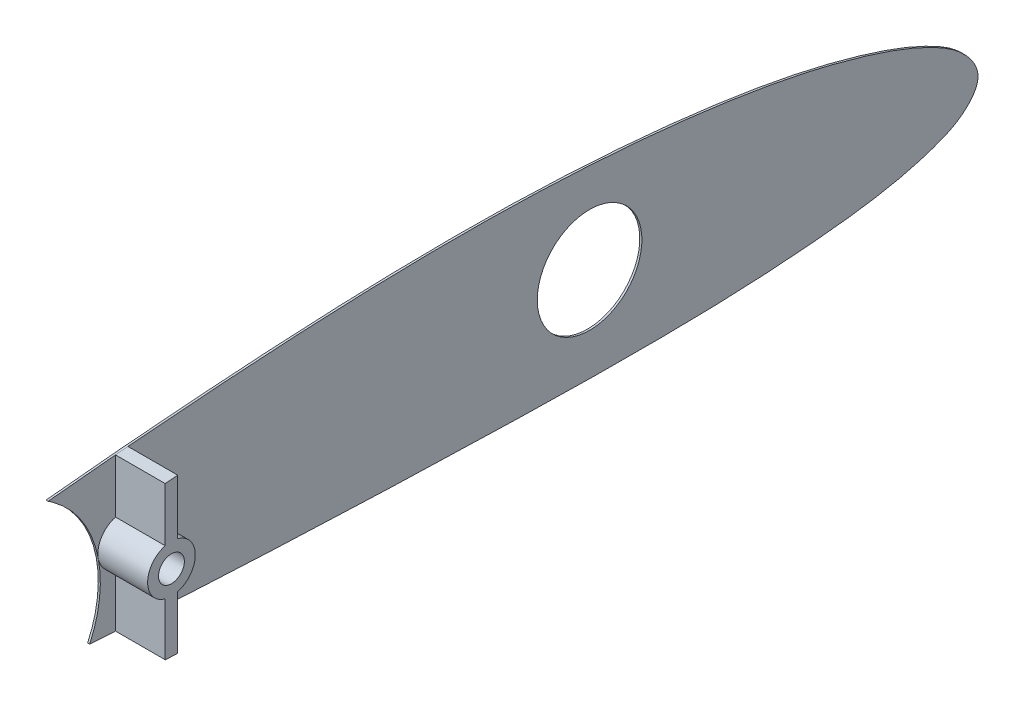
SolidWorks part; units mm, degrees
material "ABS"
ref_plane "Front Plane" through (0, 0, 0) normal (0, 0, 1) x (1, 0, 0)
ref_plane "Top Plane" through (0, 0, 0) normal (0, 1, 0) x (1, 0, 0)
ref_plane "Right Plane" through (0, 0, 0) normal (1, 0, 0) x (0, 0, -1)
body saved out of another part "Stock-NACA2412_3Dmodel_test-1" rebuild error yes
sketch "Sketch15" plane through (1117, 0, 0) normal (-1, 0, 0) x (0, 0, 1)
  line L0 (74.9825, 5.5405) -> (165.3194, 5.5405) construction
  line L1 (165.3194, 5.5405) -> (165.3194, 29.5787) construction
  line L2 (166.5194, 9.9812) -> (166.5194, 20.3782)
  line L3 (166.5194, 1.0998) -> (166.5194, -9.0912)
  line L4 (164.1194, 1.0998) -> (164.1194, -9.2318)
  line L5 (164.1194, 20.5898) -> (164.1194, 9.9812)
  circle A0 centre (74.9825, 5.5405) radius 10.1 construction
  circle A1 centre (165.3194, 5.5405) radius 2.5
  arc A2 (166.5194, 9.9812) -> (166.5194, 1.0998) centre (165.3194, 5.5405) ccw
  arc A3 (164.1194, 1.0998) -> (164.1194, 9.9812) centre (165.3194, 5.5405) ccw
  circle A4 centre (74.9825, 5.5405) radius 10.1 construction
  circle A5 centre (74.9825, 5.5405) radius 10.1 construction
  arc A6 (178.5261, 18.427) -> (171.5103, -8.7945) centre (191.6081, 0.5405) ccw construction
  spline S0 degree 3 poles (166.5194, -9.0912) (165.7194, -9.1378) (164.9194, -9.1847) (164.1194, -9.2318) knots 0.777434 0.777434 0.777434 0.777434 0.781364 0.781364 0.781364 0.781364
  spline S1 degree 3 poles (164.1194, 20.5898) (164.9193, 20.5183) (165.7193, 20.4478) (166.5194, 20.3782) knots 0.220717 0.220717 0.220717 0.220717 0.224654 0.224654 0.224654 0.224654
  spline S2 degree 3 poles (179.5417, 19.1273) (169.7083, 20.1389) (149.8799, 21.8677) (120.0263, 23.6351) (94.9907, 23.9358) (74.9819, 23.1075) (59.963, 21.8937) (44.9251, 19.9716) (32.4099, 17.6048) (22.4325, 14.927) (14.8683, 12.4925) (8.4595, 9.6559) (2.9313, 6.2169) (-1.8895, 0.2696) (3.118, -4.9579) (8.5428, -7.3422) (14.9234, -9.1532) (22.4628, -10.4518) (32.4801, -11.56) (44.9841, -12.4129) (59.9982, -12.7549) (75.0016, -12.7072) (95.0035, -12.2657) (120.0081, -11.4712) (147.1778, -10.2191) (164.3414, -9.2244) (171.5102, -8.7945) knots 0.210464 0.210464 0.210464 0.210464 0.258935 0.308047 0.357083 0.381622 0.406221 0.430945 0.455929 0.46862 0.481537 0.49501 0.502394 0.514589 0.524739 0.531581 0.544366 0.556821 0.569162 0.593739 0.618265 0.642782 0.667305 0.716364 0.765451 0.800666 0.800666 0.800666 0.800666 construction
  dimension "D2" = 4.6
  dimension "D3" = 5
  dimension "D1" = 1.2
extrude "Boss-Extrude10" add sketch "Sketch15" against normal blind 10 contours A3 A2 A1 | A2 L2 L5 | A2 | A2 | A2 L4 L3 | S1 L5 L2 | S0 L3 L4 | A3 region at (1117, 15.2857, 165.3153) region at (1117, 5.5405, 169.7893) region at (1117, -4.0841, 165.3166)
sketch "Sketch16" plane through (1117, 0, 0) normal (-1, 0, 0) x (0, 0, 1)
  circle A0 centre (165.3194, 5.5405) radius 2.5 construction
  circle A1 centre (165.3194, 5.5405) radius 2.5
extrude "Cut-Extrude4" cut sketch "Sketch16" against normal up to surface (26.592 mm away) rebuild error yes
sketch "Sketch17" plane through (1117, 0, 0) normal (-1, 0, 0) x (0, 0, 1)
  line L2 (178.5261, 18.427) -> (178.5264, 18.427)
  line L4 (178.5261, 18.427) -> (178.5264, 18.427)
  arc A0 (178.5261, 18.427) -> (171.5102, -8.7945) centre (191.6081, 0.5405) ccw
  arc A1 (179.5417, 19.1273) -> (178.5264, 18.427) centre (191.6474, 0.4894) ccw
  arc A2 (178.5261, 18.427) -> (171.5102, -8.7945) centre (191.6081, 0.5405) ccw
  arc A3 (179.5417, 19.1273) -> (178.5264, 18.427) centre (191.6474, 0.4894) ccw
  circle A4 centre (74.9825, 5.5405) radius 10.1 construction
  circle A5 centre (74.9825, 5.5405) radius 10.1
  circle A6 centre (165.3194, 5.5405) radius 2.5 construction
  circle A7 centre (165.3194, 5.5405) radius 2.5
  spline S4 degree 3 poles (-1143.7489, -13537.854) (1764.0954, -1100.5238) (984.7299, -27.5584) (120.0263, 23.6351) (94.9907, 23.9358) (74.9819, 23.1075) (59.963, 21.8937) (44.9251, 19.9716) (32.4099, 17.6048) (22.4325, 14.927) (14.8683, 12.4925) (8.4595, 9.6559) (2.9313, 6.2169) (-1.8895, 0.2696) (3.118, -4.9579) (8.5428, -7.3422) (14.9234, -9.1532) (22.4628, -10.4518) (32.4801, -11.56) (44.9841, -12.4129) (59.9982, -12.7549) (75.0016, -12.7072) (95.0035, -12.2657) (120.0081, -11.4712) (772.1072, 18.5804) (1398.5797, 332.2655) (2756.3186, -13524.6249) knots -3.889697 -3.889697 -3.889697 -3.889697 0.258935 0.308047 0.357083 0.381622 0.406221 0.430945 0.455929 0.46862 0.481537 0.49501 0.502394 0.514589 0.524739 0.531581 0.544366 0.556821 0.569162 0.593739 0.618265 0.642782 0.667305 0.716364 0.765451 3.868109 3.868109 3.868109 3.868109 only from (179.5417, 19.1273) to (171.5102, -8.7945)
  spline S6 degree 3 poles (179.5417, 19.1273) (169.7083, 20.1389) (149.8799, 21.8677) (120.0263, 23.6351) (94.9907, 23.9358) (74.9819, 23.1075) (59.963, 21.8937) (44.9251, 19.9716) (32.4099, 17.6048) (22.4325, 14.927) (14.8683, 12.4925) (8.4595, 9.6559) (2.9313, 6.2169) (-1.8895, 0.2696) (3.118, -4.9579) (8.5428, -7.3422) (14.9234, -9.1532) (22.4628, -10.4518) (32.4801, -11.56) (44.9841, -12.4129) (59.9982, -12.7549) (75.0016, -12.7072) (95.0035, -12.2657) (120.0081, -11.4712) (147.1778, -10.2191) (164.3414, -9.2244) (171.5102, -8.7945) knots 0.210464 0.210464 0.210464 0.210464 0.258935 0.308047 0.357083 0.381622 0.406221 0.430945 0.455929 0.46862 0.481537 0.49501 0.502394 0.514589 0.524739 0.531581 0.544366 0.556821 0.569162 0.593739 0.618265 0.642782 0.667305 0.716364 0.765451 0.800666 0.800666 0.800666 0.800666
  dimension "D1" = 0
extrude "Boss-Extrude11" add sketch "Sketch17" against normal blind 0.4
sketch "Sketch18" plane through (1335, 0, 0) normal (1, 0, 0) x (0, 0, -1)
  line L0 (-166.5194, 1.0998) -> (-166.5194, -9.0912) construction
  line L1 (-164.1194, 1.0998) -> (-164.1194, -9.2318) construction
  line L2 (-164.1194, 20.5898) -> (-164.1194, 9.9812) construction
  line L3 (-166.5194, 9.9812) -> (-166.5194, 20.3782) construction
  line L4 (-166.5194, 1.0998) -> (-166.5194, -9.0912)
  line L5 (-164.1194, 1.0998) -> (-164.1194, -9.2318)
  line L6 (-164.1194, 20.5898) -> (-164.1194, 9.9812)
  line L7 (-166.5194, 9.9812) -> (-166.5194, 20.3782)
  arc A0 (-164.1194, -9.2318) -> (-166.5194, -9.0912) centre (-386.3474, -3783.4872) ccw construction
  circle A1 centre (-165.3194, 5.5405) radius 2.5 construction
  arc A2 (-166.5194, 1.0998) -> (-166.5194, 9.9812) centre (-165.3194, 5.5405) ccw construction
  arc A3 (-164.1194, 9.9812) -> (-164.1194, 1.0998) centre (-165.3194, 5.5405) ccw construction
  arc A4 (-166.5194, 20.3782) -> (-164.1194, 20.5898) centre (-253.8097, 1024.2016) ccw construction
  arc A5 (-164.1194, -9.2318) -> (-166.5194, -9.0912) centre (-386.3474, -3783.4872) ccw
  circle A6 centre (-165.3194, 5.5405) radius 2.5
  arc A7 (-166.5194, 1.0998) -> (-166.5194, 9.9812) centre (-165.3194, 5.5405) ccw
  arc A8 (-164.1194, 9.9812) -> (-164.1194, 1.0998) centre (-165.3194, 5.5405) ccw
  arc A9 (-166.5194, 20.3782) -> (-164.1194, 20.5898) centre (-253.8097, 1024.2016) ccw
extrude "Boss-Extrude12" add sketch "Sketch18" against normal up to surface (35.2162 mm away) rebuild error yes
sketch "Sketch19" plane through (1335, 0, 0) normal (1, 0, 0) x (0, 0, -1)
  circle A0 centre (-165.3194, 5.5405) radius 2.5 construction
  circle A1 centre (-165.3194, 5.5405) radius 2.5
extrude "Cut-Extrude5" cut sketch "Sketch19" against normal up to surface (38.9162 mm away) rebuild error yes
